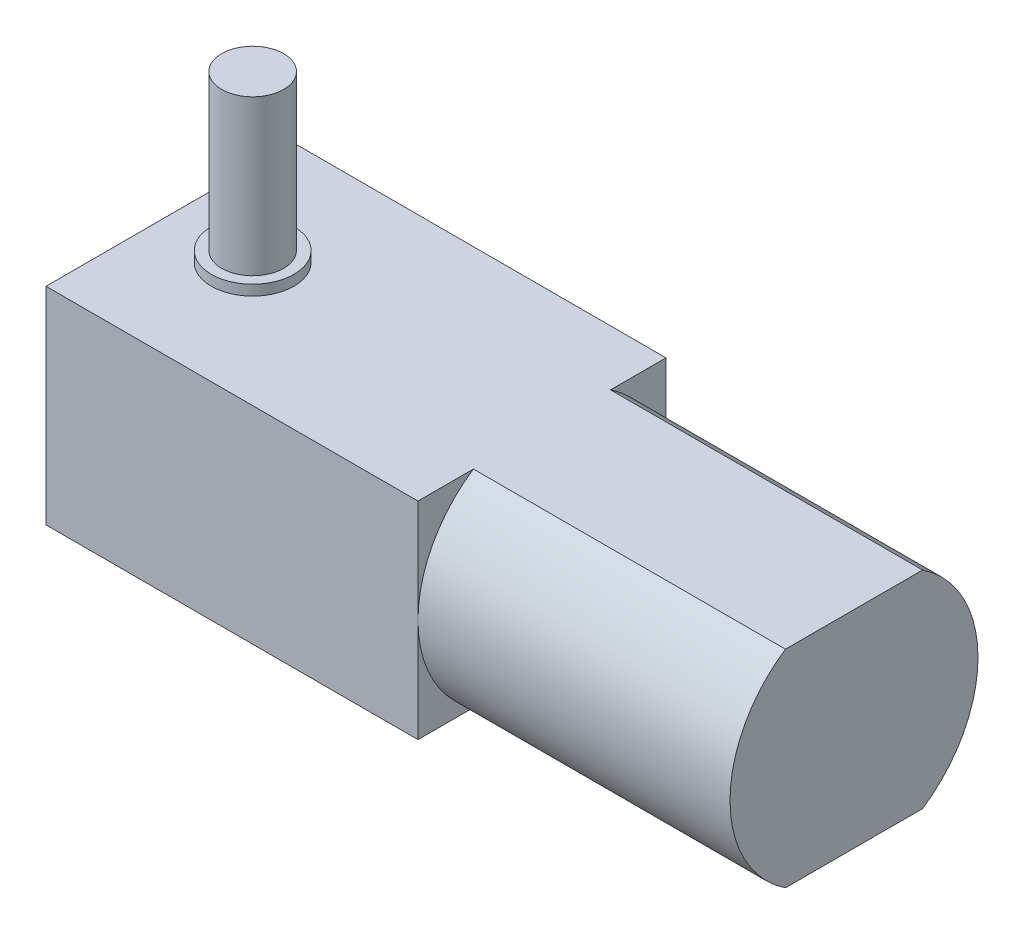
SolidWorks part; units mm, degrees
ref_plane "Front Plane" through (0, 0, 0) normal (0, 0, 1) x (1, 0, 0)
ref_plane "Top Plane" through (0, 0, 0) normal (0, 1, 0) x (1, 0, 0)
ref_plane "Right Plane" through (0, 0, 0) normal (1, 0, 0) x (0, 0, -1)
sketch "Sketch1" plane through (0, 0, 0) normal (1, 0, 0) x (0, 0, -1)
  line L1 (-6, 5) -> (6, 5)
  line L2 (-6, 5) -> (-6, -5)
  line L3 (-6, -5) -> (6, -5)
  line L4 (6, 5) -> (6, -5)
  circle A0 centre (0, 0) radius 6
  point P7 (6, 0)
  point P9 (0, 5)
  dimension "D1" = 12
  dimension "D2" = 10
  dimension "D3" = 12
extrude "Boss-Extrude1" add sketch "Sketch1" along normal blind 15.1 contours L1 A0 L3 region at (0, 0, 0)
extrude "Boss-Extrude2" add sketch "Sketch1<3>" against normal blind 18 contours A0 L1 L2 | L1 A0 L3 | A0 L4 L1 | A0 L2 L3 | A0 L3 L4 region at (0, 3.8127, 5.2392) region at (0, 0, 0) region at (0, -3.8127, 5.2392) region at (0, 3.8127, -5.2392) region at (0, -3.8127, -5.2392)
sketch "Sketch1<3>" plane through (0, 0, 0) normal (1, 0, 0) x (0, 0, -1) same geometry as "Sketch1"
sketch "Sketch2" plane through (0, 0, 0) normal (0, 1, 0) x (1, 0, 0)
  line L0 (-18, -6) -> (-18, 6) construction
  circle A0 centre (-14, 0) radius 1.5
  circle A1 centre (-14, 0) radius 2
  dimension "D1" = 3
  dimension "D3" = 4
  dimension "D2" = 4
extrude "Boss-Extrude3" add sketch "Sketch2" along normal blind 8 from surface contours A0 region at (-14, 0, 0) starting at face at (-0.725, 5, 0)
extrude "Boss-Extrude4" add sketch "Sketch2<3>" along normal blind 0.5 from surface starting at face at (-14, 5, 1.5)
sketch "Sketch2<3>" plane through (0, 0, 0) normal (0, 1, 0) x (1, 0, 0) same geometry as "Sketch2"
